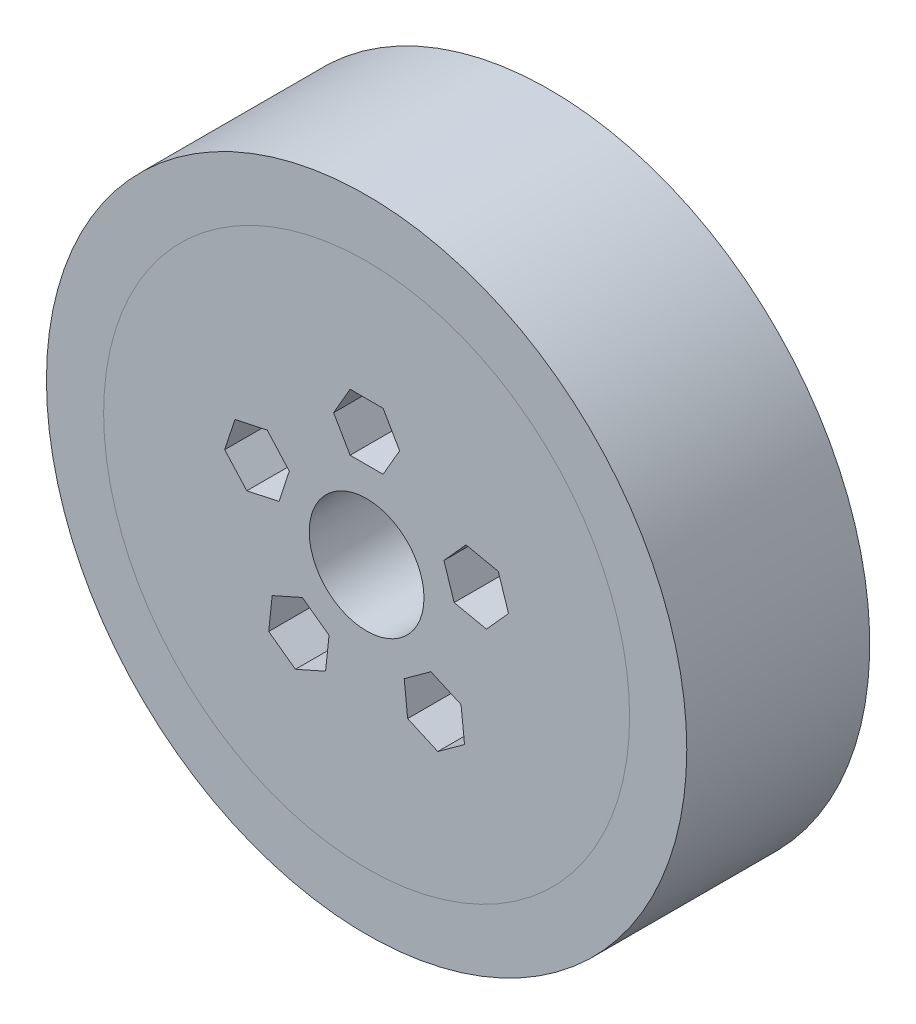
SolidWorks part; units mm, degrees
ref_plane "Front Plane" through (0, 0, 0) normal (0, 0, 1) x (1, 0, 0)
ref_plane "Top Plane" through (0, 0, 0) normal (0, 1, 0) x (1, 0, 0)
ref_plane "Right Plane" through (0, 0, 0) normal (1, 0, 0) x (0, 0, -1)
sketch "Sketch1" plane through (0, 0, 0) normal (0, 0, 1) x (1, 0, 0)
  circle A0 centre (0, 0) radius 44.45 construction
  circle A1 centre (0, 0) radius 36.5125
  circle A2 centre (0, 0) radius 7.9629
  dimension "D1" = 88.9
  dimension "D2" = 15.9258
  dimension "D3" = 7.9375
extrude "Boss-Extrude1" add sketch "Sketch1" along normal blind 25.4
sketch "Sketch3" [suppressed] plane through (0, 0, 0) normal (1, 0, 0) x (0, 0, -1)
  line L0 (-10.3109, 36.5125) -> (-7.3779, 41.5925)
  line L1 (0, 36.5125) -> (-25.4, 36.5125) construction
  line L2 (-7.3779, 41.5925) -> (-4.2029, 41.5925)
  line L3 (-4.2029, 41.5925) -> (-1.27, 36.5125)
  line L4 (0, 0) -> (0, 34.925) construction
  line L5 (0, 0) -> (16.9074, 0) construction
  line L6 (-10.3109, 36.5125) -> (-1.27, 36.5125)
  line L7 (-5.7904, 41.5925) -> (-5.7904, 36.5125) construction
  dimension "D1" = 69.85
  dimension "D2" = 5.08
  dimension "D3" = 30
  dimension "D4" = 3.175
  dimension "D5" = 1.27
revolve "Revolve1" [suppressed] add sketch "Sketch3" angle 360 about L5
sketch "Sketch4" [suppressed] plane through (0, 0, 0) normal (0, 0, 1) x (1, 0, 0)
  line L0 (0, 0) -> (-7.2225, 40.9606) construction
  line L1 (0, 0) -> (7.2225, 40.9606) construction
  line L3 (0, 41.5925) -> (0, 0) construction
  line L4 (7.3339, 41.5925) -> (-7.3339, 41.5925) construction
  line L5 (6.3403, 35.9578) -> (6.9137, 39.2096)
  line L6 (-6.9137, 39.2096) -> (-6.3403, 35.9578)
  circle A0 centre (0, 0) radius 41.5925 construction
  arc A1 (6.9137, 39.2096) -> (-6.9137, 39.2096) centre (0, 0) ccw
  arc A2 (6.3403, 35.9578) -> (-6.3403, 35.9578) centre (0, 0) ccw
  circle A4 centre (0, 0) radius 36.5125 construction
  point P11 (0, 41.5925)
  dimension "D2" = 1.778
  dimension "D1" = 20
extrude "Cut-Extrude2" [suppressed] cut sketch "Sketch4" along normal through all
fillet "Fillet1" [suppressed] radius 1.27
fillet "Fillet2" [suppressed] radius 0.762
pattern_circular "CirPattern1" [suppressed] count 14 over 360 reverse direction yes of bodies 104
split "Split1" [suppressed] bodies to split 105
pattern_linear "LPattern12" [suppressed] count 3 spacing 7.366 of bodies 110
combine bodies "Combine3" [suppressed] bodies to combine 111 114 113 112 110 117
sketch "Sketch2" plane through (0, 0, 0) normal (0, 0, 1) x (1, 0, 0)
  circle A0 centre (0, 0) radius 25.4
  circle A2 centre (0, 0) radius 7.9629 construction
  circle A3 centre (0, 0) radius 7.9629
  dimension "D1" = 50.8
extrude "Boss-Extrude3" add sketch "Sketch2" against normal blind 2.54
sketch "Sketch7" plane through (0, 0, 0) normal (0, 0, -1) x (-1, 0, 0)
  circle A0 centre (0, 0) radius 36.5125 construction
  circle A1 centre (0, 0) radius 44.45 construction
  circle A2 centre (0, 0) radius 36.5125
  circle A3 centre (0, 0) radius 44.45
extrude "Boss-Extrude2" add sketch "Sketch7" against normal up to surface (25.4 mm away) separate body up to face at (36.5125, 0, 25.4)
chamfer "Chamfer1" distance 1.27 angle 45 1 edges at (25.4, 0, -2.54)
sketch "Sketch8" plane through (0, 0, -2.54) normal (0, 0, -1) x (-1, 0, 0)
  line L54 (-3.1722, 20.1603) -> (-3.1669, 20.1266)
  line L55 (-1.56, 20.3144) -> (-1.5626, 20.3484)
  line L56 (1.5626, 20.3484) -> (1.56, 20.3144)
  line L57 (3.1669, 20.1266) -> (3.1722, 20.1603)
  line L58 (6.2131, 19.4395) -> (6.2028, 19.4071)
  line L59 (7.723, 18.8538) -> (7.7359, 18.8853)
  line L60 (10.5287, 17.4827) -> (10.5112, 17.4535)
  line L61 (11.8628, 16.5645) -> (11.8827, 16.5922)
  line L62 (14.2767, 14.5833) -> (14.2529, 14.559)
  line L63 (15.3631, 13.3822) -> (15.3888, 13.4046)
  line L64 (17.255, 10.8978) -> (17.2262, 10.8796)
  line L65 (18.0351, 9.4785) -> (18.0653, 9.4944)
  line L66 (19.3031, 6.6248) -> (19.2709, 6.6137)
  line L67 (19.7349, 5.0639) -> (19.7679, 5.0723)
  line L68 (20.3106, 1.9946) -> (20.2767, 1.9913)
  line L69 (20.3708, 0.3762) -> (20.4048, 0.3768)
  line L70 (20.2231, -2.7431) -> (20.1893, -2.7385)
  line L71 (19.9084, -4.3318) -> (19.9417, -4.339)
  line L72 (19.0454, -7.3329) -> (19.0136, -7.3207)
  line L73 (18.3728, -8.8062) -> (18.4035, -8.8209)
  line L74 (16.8409, -11.5274) -> (16.8128, -11.5082)
  line L75 (15.8467, -12.8059) -> (15.8732, -12.8273)
  line L76 (13.7286, -15.1005) -> (13.7056, -15.0753)
  line L77 (12.4663, -16.1152) -> (12.4872, -16.1422)
  line L78 (9.8761, -17.8595) -> (9.8596, -17.8297)
  line L79 (8.4139, -18.5558) -> (8.4279, -18.5868)
  line L80 (5.4912, -19.6557) -> (5.482, -19.6229)
  line L81 (3.9078, -19.996) -> (3.9143, -20.0294)
  line L82 (0.8103, -20.3922) -> (0.8089, -20.3582)
  line L83 (-0.8089, -20.3582) -> (-0.8103, -20.3922)
  line L84 (-3.9143, -20.0294) -> (-3.9078, -19.996)
  line L85 (-5.482, -19.6229) -> (-5.4912, -19.6557)
  line L86 (-8.4279, -18.5868) -> (-8.4139, -18.5558)
  line L87 (-9.8596, -17.8297) -> (-9.8761, -17.8595)
  line L88 (-12.4872, -16.1422) -> (-12.4663, -16.1152)
  line L89 (-13.7056, -15.0753) -> (-13.7286, -15.1005)
  line L90 (-15.8732, -12.8273) -> (-15.8467, -12.8059)
  line L91 (-16.8128, -11.5082) -> (-16.8409, -11.5274)
  line L92 (-18.4035, -8.8209) -> (-18.3728, -8.8062)
  line L93 (-19.0136, -7.3207) -> (-19.0454, -7.3329)
  line L94 (-19.9417, -4.339) -> (-19.9084, -4.3318)
  line L95 (-20.1893, -2.7385) -> (-20.2231, -2.7431)
  line L96 (-20.4048, 0.3768) -> (-20.3708, 0.3762)
  line L97 (-20.2767, 1.9913) -> (-20.3106, 1.9946)
  line L98 (-19.7679, 5.0723) -> (-19.7349, 5.0639)
  line L99 (-19.2709, 6.6137) -> (-19.3031, 6.6248)
  line L100 (-18.0653, 9.4944) -> (-18.0351, 9.4785)
  line L101 (-17.2262, 10.8796) -> (-17.255, 10.8978)
  line L102 (-15.3888, 13.4046) -> (-15.3631, 13.3822)
  line L103 (-14.2529, 14.559) -> (-14.2767, 14.5833)
  line L104 (-11.8827, 16.5922) -> (-11.8628, 16.5645)
  line L105 (-10.5112, 17.4535) -> (-10.5287, 17.4827)
  line L106 (-7.7359, 18.8853) -> (-7.723, 18.8538)
  line L107 (-6.2028, 19.4071) -> (-6.2131, 19.4395)
  line L108 (-3.1722, 20.1603) -> (-3.1669, 20.1266)
  line L109 (-1.56, 20.3144) -> (-1.5626, 20.3484)
  line L110 (1.5626, 20.3484) -> (1.56, 20.3144)
  line L111 (3.1669, 20.1266) -> (3.1722, 20.1603)
  line L112 (6.2131, 19.4395) -> (6.2028, 19.4071)
  line L113 (7.723, 18.8538) -> (7.7359, 18.8853)
  line L114 (10.5287, 17.4827) -> (10.5112, 17.4535)
  line L115 (11.8628, 16.5645) -> (11.8827, 16.5922)
  line L116 (14.2767, 14.5833) -> (14.2529, 14.559)
  line L117 (15.3631, 13.3822) -> (15.3888, 13.4046)
  line L118 (17.255, 10.8978) -> (17.2262, 10.8796)
  line L119 (18.0351, 9.4785) -> (18.0653, 9.4944)
  line L120 (19.3031, 6.6248) -> (19.2709, 6.6137)
  line L121 (19.7349, 5.0639) -> (19.7679, 5.0723)
  line L122 (20.3106, 1.9946) -> (20.2767, 1.9913)
  line L123 (20.3708, 0.3762) -> (20.4048, 0.3768)
  line L124 (20.2231, -2.7431) -> (20.1893, -2.7385)
  line L125 (19.9084, -4.3318) -> (19.9417, -4.339)
  line L126 (19.0454, -7.3329) -> (19.0136, -7.3207)
  line L127 (18.3728, -8.8062) -> (18.4035, -8.8209)
  line L128 (16.8409, -11.5274) -> (16.8128, -11.5082)
  line L129 (15.8467, -12.8059) -> (15.8732, -12.8273)
  line L130 (13.7286, -15.1005) -> (13.7056, -15.0753)
  line L131 (12.4663, -16.1152) -> (12.4872, -16.1422)
  line L132 (9.8761, -17.8595) -> (9.8596, -17.8297)
  line L133 (8.4139, -18.5558) -> (8.4279, -18.5868)
  line L134 (5.4912, -19.6557) -> (5.482, -19.6229)
  line L135 (3.9078, -19.996) -> (3.9143, -20.0294)
  line L136 (0.8103, -20.3922) -> (0.8089, -20.3582)
  line L137 (-0.8089, -20.3582) -> (-0.8103, -20.3922)
  line L138 (-3.9143, -20.0294) -> (-3.9078, -19.996)
  line L139 (-5.482, -19.6229) -> (-5.4912, -19.6557)
  line L140 (-8.4279, -18.5868) -> (-8.4139, -18.5558)
  line L141 (-9.8596, -17.8297) -> (-9.8761, -17.8595)
  line L142 (-12.4872, -16.1422) -> (-12.4663, -16.1152)
  line L143 (-13.7056, -15.0753) -> (-13.7286, -15.1005)
  line L144 (-15.8732, -12.8273) -> (-15.8467, -12.8059)
  line L145 (-16.8128, -11.5082) -> (-16.8409, -11.5274)
  line L146 (-18.4035, -8.8209) -> (-18.3728, -8.8062)
  line L147 (-19.0136, -7.3207) -> (-19.0454, -7.3329)
  line L148 (-19.9417, -4.339) -> (-19.9084, -4.3318)
  line L149 (-20.1893, -2.7385) -> (-20.2231, -2.7431)
  line L150 (-20.4048, 0.3768) -> (-20.3708, 0.3762)
  line L151 (-20.2767, 1.9913) -> (-20.3106, 1.9946)
  line L152 (-19.7679, 5.0723) -> (-19.7349, 5.0639)
  line L153 (-19.2709, 6.6137) -> (-19.3031, 6.6248)
  line L154 (-18.0653, 9.4944) -> (-18.0351, 9.4785)
  line L155 (-17.2262, 10.8796) -> (-17.255, 10.8978)
  line L156 (-15.3888, 13.4046) -> (-15.3631, 13.3822)
  line L157 (-14.2529, 14.559) -> (-14.2767, 14.5833)
  line L158 (-11.8827, 16.5922) -> (-11.8628, 16.5645)
  line L159 (-10.5112, 17.4535) -> (-10.5287, 17.4827)
  line L160 (-7.7359, 18.8853) -> (-7.723, 18.8538)
  line L161 (-6.2028, 19.4071) -> (-6.2131, 19.4395)
  arc A108 (-2.7438, 20.7336) -> (-3.1722, 20.1603) centre (-2.6782, 20.238) ccw
  arc A109 (-2.1116, 20.8075) -> (-2.7438, 20.7336) centre (0, 0) ccw
  arc A110 (-1.5626, 20.3484) -> (-2.1116, 20.8075) centre (-2.0611, 20.3101) ccw
  arc A111 (-1.56, 20.3144) -> (1.56, 20.3144) centre (0, 20.3144) ccw
  arc A112 (2.1116, 20.8075) -> (1.5626, 20.3484) centre (2.0611, 20.3101) ccw
  arc A113 (2.7438, 20.7336) -> (2.1116, 20.8075) centre (0, 0) ccw
  arc A114 (3.1722, 20.1603) -> (2.7438, 20.7336) centre (2.6782, 20.238) ccw
  arc A115 (3.1669, 20.1266) -> (6.2028, 19.4071) centre (4.6848, 19.7668) ccw
  arc A116 (6.8533, 19.7597) -> (6.2131, 19.4395) centre (6.6894, 19.2873) ccw
  arc A117 (7.4514, 19.542) -> (6.8533, 19.7597) centre (0, 0) ccw
  arc A118 (7.7359, 18.8853) -> (7.4514, 19.542) centre (7.2733, 19.0748) ccw
  arc A119 (7.723, 18.8538) -> (10.5112, 17.4535) centre (9.1171, 18.1536) ccw
  arc A120 (11.2254, 17.6466) -> (10.5287, 17.4827) centre (10.9571, 17.2247) ccw
  arc A121 (11.7572, 17.2968) -> (11.2254, 17.6466) centre (0, 0) ccw
  arc A122 (11.8827, 16.5922) -> (11.7572, 17.2968) centre (11.4762, 16.8833) ccw
  arc A123 (11.8628, 16.5645) -> (14.2529, 14.559) centre (13.0579, 15.5617) ccw
  arc A124 (14.9924, 14.5822) -> (14.2767, 14.5833) centre (14.634, 14.2336) ccw
  arc A125 (15.4292, 14.1192) -> (14.9924, 14.5822) centre (0, 0) ccw
  arc A126 (15.3888, 13.4046) -> (15.4292, 14.1192) centre (15.0604, 13.7816) ccw
  arc A127 (15.3631, 13.3822) -> (17.2262, 10.8796) centre (16.2947, 12.1309) ccw
  arc A128 (17.9512, 10.7316) -> (17.255, 10.8978) centre (17.522, 10.4751) ccw
  arc A129 (18.2695, 10.1804) -> (17.9512, 10.7316) centre (0, 0) ccw
  arc A130 (18.0653, 9.4944) -> (18.2695, 10.1804) centre (17.8327, 9.937) ccw
  arc A131 (18.0351, 9.4785) -> (19.2709, 6.6137) centre (18.653, 8.0461) ccw
  arc A132 (19.9422, 6.3025) -> (19.3031, 6.6248) centre (19.4654, 6.1518) ccw
  arc A133 (20.1248, 5.6927) -> (19.9422, 6.3025) centre (0, 0) ccw
  arc A134 (19.7679, 5.0723) -> (20.1248, 5.6927) centre (19.6436, 5.5566) ccw
  arc A135 (19.7349, 5.0639) -> (20.2767, 1.9913) centre (20.0058, 3.5276) ccw
  arc A136 (20.8581, 1.5336) -> (20.3106, 1.9946) centre (20.3595, 1.497) ccw
  arc A137 (20.8951, 0.8982) -> (20.8581, 1.5336) centre (0, 0) ccw
  arc A138 (20.4048, 0.3768) -> (20.8951, 0.8982) centre (20.3956, 0.8767) ccw
  arc A139 (20.3708, 0.3762) -> (20.1893, -2.7385) centre (20.28, -1.1812) ccw
  arc A140 (20.6496, -3.3179) -> (20.2231, -2.7431) centre (20.1559, -3.2386) ccw
  arc A141 (20.539, -3.9448) -> (20.6496, -3.3179) centre (0, 0) ccw
  arc A142 (19.9417, -4.339) -> (20.539, -3.9448) centre (20.048, -3.8505) ccw
  arc A143 (19.9084, -4.3318) -> (19.0136, -7.3207) centre (19.461, -5.8262) ccw
  arc A144 (19.3278, -7.9906) -> (19.0454, -7.3329) centre (18.8657, -7.7996) ccw
  arc A145 (19.0757, -8.5751) -> (19.3278, -7.9906) centre (0, 0) ccw
  arc A146 (18.4035, -8.8209) -> (19.0757, -8.5751) centre (18.6196, -8.37) ccw
  arc A147 (18.3728, -8.8062) -> (16.8128, -11.5082) centre (17.5928, -10.1572) ccw
  arc A148 (16.9641, -12.2325) -> (16.8409, -11.5274) centre (16.5585, -11.94) ccw
  arc A149 (16.5839, -12.7431) -> (16.9641, -12.2325) centre (0, 0) ccw
  arc A150 (15.8732, -12.8273) -> (16.5839, -12.7431) centre (16.1875, -12.4384) ccw
  arc A151 (15.8467, -12.8059) -> (13.7056, -15.0753) centre (14.7762, -13.9406) ccw
  arc A152 (13.6858, -15.8149) -> (13.7286, -15.1005) centre (13.3586, -15.4369) ccw
  arc A153 (13.1982, -16.2241) -> (13.6858, -15.8149) centre (0, 0) ccw
  arc A154 (12.4872, -16.1422) -> (13.1982, -16.2241) centre (12.8826, -15.8362) ccw
  arc A155 (12.4663, -16.1152) -> (9.8596, -17.8297) centre (11.163, -16.9724) ccw
  arc A156 (9.6697, -18.5448) -> (9.8761, -17.8595) centre (9.4385, -18.1015) ccw
  arc A157 (9.1009, -18.8305) -> (9.6697, -18.5448) centre (0, 0) ccw
  arc A158 (8.4279, -18.5868) -> (9.1009, -18.8305) centre (8.8833, -18.3803) ccw
  arc A159 (8.4139, -18.5558) -> (5.482, -19.6229) centre (6.9479, -19.0893) ccw
  arc A160 (5.1323, -20.2749) -> (5.4912, -19.6557) centre (5.0096, -19.7902) ccw
  arc A161 (4.513, -20.4217) -> (5.1323, -20.2749) centre (0, 0) ccw
  arc A162 (3.9143, -20.0294) -> (4.513, -20.4217) centre (4.4051, -19.9335) ccw
  arc A163 (3.9078, -19.996) -> (0.8089, -20.3582) centre (2.3584, -20.1771) ccw
  arc A164 (0.3183, -20.912) -> (0.8103, -20.3922) centre (0.3107, -20.4121) ccw
  arc A165 (-0.3183, -20.912) -> (0.3183, -20.912) centre (0, 0) ccw
  arc A166 (-0.8103, -20.3922) -> (-0.3183, -20.912) centre (-0.3107, -20.4121) ccw
  arc A167 (-0.8089, -20.3582) -> (-3.9078, -19.996) centre (-2.3584, -20.1771) ccw
  arc A168 (-4.513, -20.4217) -> (-3.9143, -20.0294) centre (-4.4051, -19.9335) ccw
  arc A169 (-5.1323, -20.2749) -> (-4.513, -20.4217) centre (0, 0) ccw
  arc A170 (-5.4912, -19.6557) -> (-5.1323, -20.2749) centre (-5.0096, -19.7902) ccw
  arc A171 (-5.482, -19.6229) -> (-8.4139, -18.5558) centre (-6.9479, -19.0893) ccw
  arc A172 (-9.1009, -18.8305) -> (-8.4279, -18.5868) centre (-8.8833, -18.3803) ccw
  arc A173 (-9.6697, -18.5448) -> (-9.1009, -18.8305) centre (0, 0) ccw
  arc A174 (-9.8761, -17.8595) -> (-9.6697, -18.5448) centre (-9.4385, -18.1015) ccw
  arc A175 (-9.8596, -17.8297) -> (-12.4663, -16.1152) centre (-11.163, -16.9724) ccw
  arc A176 (-13.1982, -16.2241) -> (-12.4872, -16.1422) centre (-12.8826, -15.8362) ccw
  arc A177 (-13.6858, -15.8149) -> (-13.1982, -16.2241) centre (0, 0) ccw
  arc A178 (-13.7286, -15.1005) -> (-13.6858, -15.8149) centre (-13.3586, -15.4369) ccw
  arc A179 (-13.7056, -15.0753) -> (-15.8467, -12.8059) centre (-14.7762, -13.9406) ccw
  arc A180 (-16.5839, -12.7431) -> (-15.8732, -12.8273) centre (-16.1875, -12.4384) ccw
  arc A181 (-16.9641, -12.2325) -> (-16.5839, -12.7431) centre (0, 0) ccw
  arc A182 (-16.8409, -11.5274) -> (-16.9641, -12.2325) centre (-16.5585, -11.94) ccw
  arc A183 (-16.8128, -11.5082) -> (-18.3728, -8.8062) centre (-17.5928, -10.1572) ccw
  arc A184 (-19.0757, -8.5751) -> (-18.4035, -8.8209) centre (-18.6196, -8.37) ccw
  arc A185 (-19.3278, -7.9906) -> (-19.0757, -8.5751) centre (0, 0) ccw
  arc A186 (-19.0454, -7.3329) -> (-19.3278, -7.9906) centre (-18.8657, -7.7996) ccw
  arc A187 (-19.0136, -7.3207) -> (-19.9084, -4.3318) centre (-19.461, -5.8262) ccw
  arc A188 (-20.539, -3.9448) -> (-19.9417, -4.339) centre (-20.048, -3.8505) ccw
  arc A189 (-20.6496, -3.3179) -> (-20.539, -3.9448) centre (0, 0) ccw
  arc A190 (-20.2231, -2.7431) -> (-20.6496, -3.3179) centre (-20.1559, -3.2386) ccw
  arc A191 (-20.1893, -2.7385) -> (-20.3708, 0.3762) centre (-20.28, -1.1812) ccw
  arc A192 (-20.8951, 0.8982) -> (-20.4048, 0.3768) centre (-20.3956, 0.8767) ccw
  arc A193 (-20.8581, 1.5336) -> (-20.8951, 0.8982) centre (0, 0) ccw
  arc A194 (-20.3106, 1.9946) -> (-20.8581, 1.5336) centre (-20.3595, 1.497) ccw
  arc A195 (-20.2767, 1.9913) -> (-19.7349, 5.0639) centre (-20.0058, 3.5276) ccw
  arc A196 (-20.1248, 5.6927) -> (-19.7679, 5.0723) centre (-19.6436, 5.5566) ccw
  arc A197 (-19.9422, 6.3025) -> (-20.1248, 5.6927) centre (0, 0) ccw
  arc A198 (-19.3031, 6.6248) -> (-19.9422, 6.3025) centre (-19.4654, 6.1518) ccw
  arc A199 (-19.2709, 6.6137) -> (-18.0351, 9.4785) centre (-18.653, 8.0461) ccw
  arc A200 (-18.2695, 10.1804) -> (-18.0653, 9.4944) centre (-17.8327, 9.937) ccw
  arc A201 (-17.9512, 10.7316) -> (-18.2695, 10.1804) centre (0, 0) ccw
  arc A202 (-17.255, 10.8978) -> (-17.9512, 10.7316) centre (-17.522, 10.4751) ccw
  arc A203 (-17.2262, 10.8796) -> (-15.3631, 13.3822) centre (-16.2947, 12.1309) ccw
  arc A204 (-15.4292, 14.1192) -> (-15.3888, 13.4046) centre (-15.0604, 13.7816) ccw
  arc A205 (-14.9924, 14.5822) -> (-15.4292, 14.1192) centre (0, 0) ccw
  arc A206 (-14.2767, 14.5833) -> (-14.9924, 14.5822) centre (-14.634, 14.2336) ccw
  arc A207 (-14.2529, 14.559) -> (-11.8628, 16.5645) centre (-13.0579, 15.5617) ccw
  arc A208 (-11.7572, 17.2968) -> (-11.8827, 16.5922) centre (-11.4762, 16.8833) ccw
  arc A209 (-11.2254, 17.6466) -> (-11.7572, 17.2968) centre (0, 0) ccw
  arc A210 (-10.5287, 17.4827) -> (-11.2254, 17.6466) centre (-10.9571, 17.2247) ccw
  arc A211 (-10.5112, 17.4535) -> (-7.723, 18.8538) centre (-9.1171, 18.1536) ccw
  arc A212 (-7.4514, 19.542) -> (-7.7359, 18.8853) centre (-7.2733, 19.0748) ccw
  arc A213 (-6.8533, 19.7597) -> (-7.4514, 19.542) centre (0, 0) ccw
  arc A214 (-6.2131, 19.4395) -> (-6.8533, 19.7597) centre (-6.6894, 19.2873) ccw
  arc A215 (-6.2028, 19.4071) -> (-3.1669, 20.1266) centre (-4.6848, 19.7668) ccw
  arc A216 (-2.7438, 20.7336) -> (-3.1722, 20.1603) centre (-2.6782, 20.238) ccw
  arc A217 (-2.1116, 20.8075) -> (-2.7438, 20.7336) centre (0, 0) ccw
  arc A218 (-1.5626, 20.3484) -> (-2.1116, 20.8075) centre (-2.0611, 20.3101) ccw
  arc A219 (-1.56, 20.3144) -> (1.56, 20.3144) centre (0, 20.3144) ccw
  arc A220 (2.1116, 20.8075) -> (1.5626, 20.3484) centre (2.0611, 20.3101) ccw
  arc A221 (2.7438, 20.7336) -> (2.1116, 20.8075) centre (0, 0) ccw
  arc A222 (3.1722, 20.1603) -> (2.7438, 20.7336) centre (2.6782, 20.238) ccw
  arc A223 (3.1669, 20.1266) -> (6.2028, 19.4071) centre (4.6848, 19.7668) ccw
  arc A224 (6.8533, 19.7597) -> (6.2131, 19.4395) centre (6.6894, 19.2873) ccw
  arc A225 (7.4514, 19.542) -> (6.8533, 19.7597) centre (0, 0) ccw
  arc A226 (7.7359, 18.8853) -> (7.4514, 19.542) centre (7.2733, 19.0748) ccw
  arc A227 (7.723, 18.8538) -> (10.5112, 17.4535) centre (9.1171, 18.1536) ccw
  arc A228 (11.2254, 17.6466) -> (10.5287, 17.4827) centre (10.9571, 17.2247) ccw
  arc A229 (11.7572, 17.2968) -> (11.2254, 17.6466) centre (0, 0) ccw
  arc A230 (11.8827, 16.5922) -> (11.7572, 17.2968) centre (11.4762, 16.8833) ccw
  arc A231 (11.8628, 16.5645) -> (14.2529, 14.559) centre (13.0579, 15.5617) ccw
  arc A232 (14.9924, 14.5822) -> (14.2767, 14.5833) centre (14.634, 14.2336) ccw
  arc A233 (15.4292, 14.1192) -> (14.9924, 14.5822) centre (0, 0) ccw
  arc A234 (15.3888, 13.4046) -> (15.4292, 14.1192) centre (15.0604, 13.7816) ccw
  arc A235 (15.3631, 13.3822) -> (17.2262, 10.8796) centre (16.2947, 12.1309) ccw
  arc A236 (17.9512, 10.7316) -> (17.255, 10.8978) centre (17.522, 10.4751) ccw
  arc A237 (18.2695, 10.1804) -> (17.9512, 10.7316) centre (0, 0) ccw
  arc A238 (18.0653, 9.4944) -> (18.2695, 10.1804) centre (17.8327, 9.937) ccw
  arc A239 (18.0351, 9.4785) -> (19.2709, 6.6137) centre (18.653, 8.0461) ccw
  arc A240 (19.9422, 6.3025) -> (19.3031, 6.6248) centre (19.4654, 6.1518) ccw
  arc A241 (20.1248, 5.6927) -> (19.9422, 6.3025) centre (0, 0) ccw
  arc A242 (19.7679, 5.0723) -> (20.1248, 5.6927) centre (19.6436, 5.5566) ccw
  arc A243 (19.7349, 5.0639) -> (20.2767, 1.9913) centre (20.0058, 3.5276) ccw
  arc A244 (20.8581, 1.5336) -> (20.3106, 1.9946) centre (20.3595, 1.497) ccw
  arc A245 (20.8951, 0.8982) -> (20.8581, 1.5336) centre (0, 0) ccw
  arc A246 (20.4048, 0.3768) -> (20.8951, 0.8982) centre (20.3956, 0.8767) ccw
  arc A247 (20.3708, 0.3762) -> (20.1893, -2.7385) centre (20.28, -1.1812) ccw
  arc A248 (20.6496, -3.3179) -> (20.2231, -2.7431) centre (20.1559, -3.2386) ccw
  arc A249 (20.539, -3.9448) -> (20.6496, -3.3179) centre (0, 0) ccw
  arc A250 (19.9417, -4.339) -> (20.539, -3.9448) centre (20.048, -3.8505) ccw
  arc A251 (19.9084, -4.3318) -> (19.0136, -7.3207) centre (19.461, -5.8262) ccw
  arc A252 (19.3278, -7.9906) -> (19.0454, -7.3329) centre (18.8657, -7.7996) ccw
  arc A253 (19.0757, -8.5751) -> (19.3278, -7.9906) centre (0, 0) ccw
  arc A254 (18.4035, -8.8209) -> (19.0757, -8.5751) centre (18.6196, -8.37) ccw
  arc A255 (18.3728, -8.8062) -> (16.8128, -11.5082) centre (17.5928, -10.1572) ccw
  arc A256 (16.9641, -12.2325) -> (16.8409, -11.5274) centre (16.5585, -11.94) ccw
  arc A257 (16.5839, -12.7431) -> (16.9641, -12.2325) centre (0, 0) ccw
  arc A258 (15.8732, -12.8273) -> (16.5839, -12.7431) centre (16.1875, -12.4384) ccw
  arc A259 (15.8467, -12.8059) -> (13.7056, -15.0753) centre (14.7762, -13.9406) ccw
  arc A260 (13.6858, -15.8149) -> (13.7286, -15.1005) centre (13.3586, -15.4369) ccw
  arc A261 (13.1982, -16.2241) -> (13.6858, -15.8149) centre (0, 0) ccw
  arc A262 (12.4872, -16.1422) -> (13.1982, -16.2241) centre (12.8826, -15.8362) ccw
  arc A263 (12.4663, -16.1152) -> (9.8596, -17.8297) centre (11.163, -16.9724) ccw
  arc A264 (9.6697, -18.5448) -> (9.8761, -17.8595) centre (9.4385, -18.1015) ccw
  arc A265 (9.1009, -18.8305) -> (9.6697, -18.5448) centre (0, 0) ccw
  arc A266 (8.4279, -18.5868) -> (9.1009, -18.8305) centre (8.8833, -18.3803) ccw
  arc A267 (8.4139, -18.5558) -> (5.482, -19.6229) centre (6.9479, -19.0893) ccw
  arc A268 (5.1323, -20.2749) -> (5.4912, -19.6557) centre (5.0096, -19.7902) ccw
  arc A269 (4.513, -20.4217) -> (5.1323, -20.2749) centre (0, 0) ccw
  arc A270 (3.9143, -20.0294) -> (4.513, -20.4217) centre (4.4051, -19.9335) ccw
  arc A271 (3.9078, -19.996) -> (0.8089, -20.3582) centre (2.3584, -20.1771) ccw
  arc A272 (0.3183, -20.912) -> (0.8103, -20.3922) centre (0.3107, -20.4121) ccw
  arc A273 (-0.3183, -20.912) -> (0.3183, -20.912) centre (0, 0) ccw
  arc A274 (-0.8103, -20.3922) -> (-0.3183, -20.912) centre (-0.3107, -20.4121) ccw
  arc A275 (-0.8089, -20.3582) -> (-3.9078, -19.996) centre (-2.3584, -20.1771) ccw
  arc A276 (-4.513, -20.4217) -> (-3.9143, -20.0294) centre (-4.4051, -19.9335) ccw
  arc A277 (-5.1323, -20.2749) -> (-4.513, -20.4217) centre (0, 0) ccw
  arc A278 (-5.4912, -19.6557) -> (-5.1323, -20.2749) centre (-5.0096, -19.7902) ccw
  arc A279 (-5.482, -19.6229) -> (-8.4139, -18.5558) centre (-6.9479, -19.0893) ccw
  arc A280 (-9.1009, -18.8305) -> (-8.4279, -18.5868) centre (-8.8833, -18.3803) ccw
  arc A281 (-9.6697, -18.5448) -> (-9.1009, -18.8305) centre (0, 0) ccw
  arc A282 (-9.8761, -17.8595) -> (-9.6697, -18.5448) centre (-9.4385, -18.1015) ccw
  arc A283 (-9.8596, -17.8297) -> (-12.4663, -16.1152) centre (-11.163, -16.9724) ccw
  arc A284 (-13.1982, -16.2241) -> (-12.4872, -16.1422) centre (-12.8826, -15.8362) ccw
  arc A285 (-13.6858, -15.8149) -> (-13.1982, -16.2241) centre (0, 0) ccw
  arc A286 (-13.7286, -15.1005) -> (-13.6858, -15.8149) centre (-13.3586, -15.4369) ccw
  arc A287 (-13.7056, -15.0753) -> (-15.8467, -12.8059) centre (-14.7762, -13.9406) ccw
  arc A288 (-16.5839, -12.7431) -> (-15.8732, -12.8273) centre (-16.1875, -12.4384) ccw
  arc A289 (-16.9641, -12.2325) -> (-16.5839, -12.7431) centre (0, 0) ccw
  arc A290 (-16.8409, -11.5274) -> (-16.9641, -12.2325) centre (-16.5585, -11.94) ccw
  arc A291 (-16.8128, -11.5082) -> (-18.3728, -8.8062) centre (-17.5928, -10.1572) ccw
  arc A292 (-19.0757, -8.5751) -> (-18.4035, -8.8209) centre (-18.6196, -8.37) ccw
  arc A293 (-19.3278, -7.9906) -> (-19.0757, -8.5751) centre (0, 0) ccw
  arc A294 (-19.0454, -7.3329) -> (-19.3278, -7.9906) centre (-18.8657, -7.7996) ccw
  arc A295 (-19.0136, -7.3207) -> (-19.9084, -4.3318) centre (-19.461, -5.8262) ccw
  arc A296 (-20.539, -3.9448) -> (-19.9417, -4.339) centre (-20.048, -3.8505) ccw
  arc A297 (-20.6496, -3.3179) -> (-20.539, -3.9448) centre (0, 0) ccw
  arc A298 (-20.2231, -2.7431) -> (-20.6496, -3.3179) centre (-20.1559, -3.2386) ccw
  arc A299 (-20.1893, -2.7385) -> (-20.3708, 0.3762) centre (-20.28, -1.1812) ccw
  arc A300 (-20.8951, 0.8982) -> (-20.4048, 0.3768) centre (-20.3956, 0.8767) ccw
  arc A301 (-20.8581, 1.5336) -> (-20.8951, 0.8982) centre (0, 0) ccw
  arc A302 (-20.3106, 1.9946) -> (-20.8581, 1.5336) centre (-20.3595, 1.497) ccw
  arc A303 (-20.2767, 1.9913) -> (-19.7349, 5.0639) centre (-20.0058, 3.5276) ccw
  arc A304 (-20.1248, 5.6927) -> (-19.7679, 5.0723) centre (-19.6436, 5.5566) ccw
  arc A305 (-19.9422, 6.3025) -> (-20.1248, 5.6927) centre (0, 0) ccw
  arc A306 (-19.3031, 6.6248) -> (-19.9422, 6.3025) centre (-19.4654, 6.1518) ccw
  arc A307 (-19.2709, 6.6137) -> (-18.0351, 9.4785) centre (-18.653, 8.0461) ccw
  arc A308 (-18.2695, 10.1804) -> (-18.0653, 9.4944) centre (-17.8327, 9.937) ccw
  arc A309 (-17.9512, 10.7316) -> (-18.2695, 10.1804) centre (0, 0) ccw
  arc A310 (-17.255, 10.8978) -> (-17.9512, 10.7316) centre (-17.522, 10.4751) ccw
  arc A311 (-17.2262, 10.8796) -> (-15.3631, 13.3822) centre (-16.2947, 12.1309) ccw
  arc A312 (-15.4292, 14.1192) -> (-15.3888, 13.4046) centre (-15.0604, 13.7816) ccw
  arc A313 (-14.9924, 14.5822) -> (-15.4292, 14.1192) centre (0, 0) ccw
  arc A314 (-14.2767, 14.5833) -> (-14.9924, 14.5822) centre (-14.634, 14.2336) ccw
  arc A315 (-14.2529, 14.559) -> (-11.8628, 16.5645) centre (-13.0579, 15.5617) ccw
  arc A316 (-11.7572, 17.2968) -> (-11.8827, 16.5922) centre (-11.4762, 16.8833) ccw
  arc A317 (-11.2254, 17.6466) -> (-11.7572, 17.2968) centre (0, 0) ccw
  arc A318 (-10.5287, 17.4827) -> (-11.2254, 17.6466) centre (-10.9571, 17.2247) ccw
  arc A319 (-10.5112, 17.4535) -> (-7.723, 18.8538) centre (-9.1171, 18.1536) ccw
  arc A320 (-7.4514, 19.542) -> (-7.7359, 18.8853) centre (-7.2733, 19.0748) ccw
  arc A321 (-6.8533, 19.7597) -> (-7.4514, 19.542) centre (0, 0) ccw
  arc A322 (-6.2131, 19.4395) -> (-6.8533, 19.7597) centre (-6.6894, 19.2873) ccw
  arc A323 (-6.2028, 19.4071) -> (-3.1669, 20.1266) centre (-4.6848, 19.7668) ccw
  dimension "D1" = 0
extrude "Cut-Extrude3" cut sketch "Sketch8" against normal blind 2.54
sketch "Sketch9" plane through (0, 0, 0) normal (0, 0, -1) x (-1, 0, 0)
  circle A0 centre (15.2169, 4.9443) radius 1.8288 construction
  circle A1 centre (9.4046, -12.9443) radius 1.8288 construction
  circle A2 centre (-9.4046, -12.9443) radius 1.8288 construction
  circle A3 centre (-15.2169, 4.9443) radius 1.8288 construction
  circle A4 centre (0, 16) radius 1.8288 construction
  circle A5 centre (15.2169, 4.9443) radius 1.8288
  circle A6 centre (9.4046, -12.9443) radius 1.8288
  circle A7 centre (-9.4046, -12.9443) radius 1.8288
  circle A8 centre (-15.2169, 4.9443) radius 1.8288
  circle A9 centre (0, 16) radius 1.8288
extrude "Cut-Extrude4" cut sketch "Sketch9" against normal through all
sketch "Sketch11" plane through (0, 0, 25.4) normal (0, 0, 1) x (1, 0, 0)
  line L1 (2.2914, 12.0312) -> (4.5827, 16)
  line L2 (4.5827, 16) -> (2.2914, 19.9688)
  line L3 (2.2914, 19.9688) -> (-2.2914, 19.9688)
  line L4 (-2.2914, 19.9688) -> (-4.5827, 16)
  line L5 (-4.5827, 16) -> (-2.2914, 12.0312)
  line L6 (-2.2914, 12.0312) -> (2.2914, 12.0312)
  circle A0 centre (0, 16) radius 3.9688 construction
  dimension "D1" = 7.9375
extrude "Cut-Extrude5" cut sketch "Sketch11" against normal blind 13.97
fillet "Fillet3" radius 0.508 7 edges at (1.8288, 16, 11.43) (-3.437, 14.0156, 11.43) (-3.437, 17.9844, 11.43) (0, 19.9688, 11.43) (3.437, 17.9844, 11.43) (3.437, 14.0156, 11.43) (0, 12.0312, 11.43)
pattern_circular "CirPattern3" count 5 over 360 about axis through (0, 0, 25.4) along (0, 0, 1) of "Fillet3", "Cut-Extrude5"
sketch "Sketch12" plane through (0, 0, 25.4) normal (0, 0, 1) x (1, 0, 0)
  line L0 (-13.8008, 9.3027) -> (-18.2833, 8.3499) construction
  line L1 (-10.7343, 5.8971) -> (-13.8008, 9.3027) construction
  line L2 (-12.1505, 1.5386) -> (-10.7343, 5.8971) construction
  line L3 (-16.633, 0.5858) -> (-12.1505, 1.5386) construction
  line L4 (-19.6995, 3.9915) -> (-16.633, 0.5858) construction
  line L5 (-13.1121, -10.2506) -> (-13.5911, -14.8082) construction
  line L6 (-8.9255, -8.3867) -> (-13.1121, -10.2506) construction
  line L7 (-5.218, -11.0803) -> (-8.9255, -8.3867) construction
  line L8 (-5.6971, -15.6379) -> (-5.218, -11.0803) construction
  line L9 (-9.8836, -17.5019) -> (-5.6971, -15.6379) construction
  line L10 (5.6971, -15.6379) -> (9.8836, -17.5019) construction
  line L11 (5.218, -11.0803) -> (5.6971, -15.6379) construction
  line L12 (8.9255, -8.3867) -> (5.218, -11.0803) construction
  line L13 (13.5911, -14.8082) -> (13.1121, -10.2506) construction
  line L14 (13.1121, -10.2506) -> (8.9255, -8.3867) construction
  line L15 (16.633, 0.5858) -> (19.6995, 3.9915) construction
  line L16 (12.1505, 1.5386) -> (16.633, 0.5858) construction
  line L17 (10.7343, 5.8971) -> (12.1505, 1.5386) construction
  line L18 (13.8008, 9.3027) -> (10.7343, 5.8971) construction
  line L19 (18.2833, 8.3499) -> (13.8008, 9.3027) construction
  line L20 (4.5827, 16) -> (2.2914, 19.9688) construction
  line L21 (2.2914, 12.0312) -> (4.5827, 16) construction
  line L22 (-2.2914, 12.0312) -> (2.2914, 12.0312) construction
  line L23 (-4.5827, 16) -> (-2.2914, 12.0312) construction
  line L24 (-2.2914, 19.9688) -> (-4.5827, 16) construction
  line L25 (-13.8008, 9.3027) -> (-14.9262, 9.0635)
  line L26 (-10.7343, 5.8971) -> (-13.8008, 9.3027)
  line L27 (-12.1505, 1.5386) -> (-10.7343, 5.8971)
  line L28 (-16.633, 0.5858) -> (-12.1505, 1.5386)
  line L29 (-17.4029, 1.4409) -> (-16.633, 0.5858)
  line L30 (-13.1121, -10.2506) -> (-13.2323, -11.3949)
  line L31 (-8.9255, -8.3867) -> (-13.1121, -10.2506)
  line L32 (-5.218, -11.0803) -> (-8.9255, -8.3867)
  line L33 (-5.6971, -15.6379) -> (-5.218, -11.0803)
  line L34 (-6.7482, -16.1059) -> (-5.6971, -15.6379)
  line L35 (5.6971, -15.6379) -> (6.7482, -16.1059)
  line L36 (5.218, -11.0803) -> (5.6971, -15.6379)
  line L37 (8.9255, -8.3867) -> (5.218, -11.0803)
  line L38 (13.2323, -11.3949) -> (13.1121, -10.2506)
  line L39 (13.1121, -10.2506) -> (8.9255, -8.3867)
  line L40 (16.633, 0.5858) -> (17.4029, 1.4409)
  line L41 (12.1505, 1.5386) -> (16.633, 0.5858)
  line L42 (10.7343, 5.8971) -> (12.1505, 1.5386)
  line L43 (13.8008, 9.3027) -> (10.7343, 5.8971)
  line L44 (14.9262, 9.0635) -> (13.8008, 9.3027)
  line L45 (4.5827, 16) -> (4.0074, 16.9965)
  line L46 (2.2914, 12.0312) -> (4.5827, 16)
  line L47 (-2.2914, 12.0312) -> (2.2914, 12.0312)
  line L48 (-4.5827, 16) -> (-2.2914, 12.0312)
  line L49 (-4.0074, 16.9965) -> (-4.5827, 16)
  arc A0 (-17.4029, 1.4409) -> (-13.2323, -11.3949) centre (0, 0) ccw
  circle A1 centre (0, 0) radius 7.9629 construction
  circle A2 centre (0, 0) radius 7.9629
  arc A3 (-4.0074, 16.9965) -> (-14.9262, 9.0635) centre (0, 0) ccw
  arc A4 (14.9262, 9.0635) -> (4.0074, 16.9965) centre (0, 0) ccw
  arc A5 (13.2323, -11.3949) -> (17.4029, 1.4409) centre (0, 0) ccw
  arc A6 (-6.7482, -16.1059) -> (6.7482, -16.1059) centre (0, 0) ccw
  dimension "D1" = 34.925
extrude "Boss-Extrude4" [suppressed] add sketch "Sketch12" along normal blind 3.175
